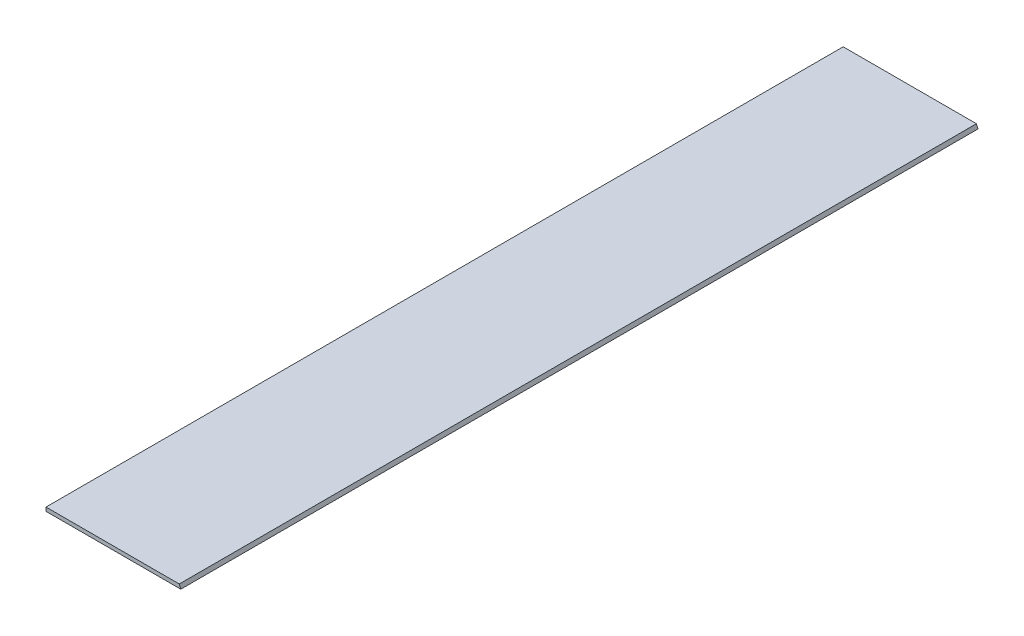
SolidWorks part; units mm, degrees
ref_plane "Front Plane" through (0, 0, 0) normal (0, 0, 1) x (1, 0, 0)
ref_plane "Top Plane" through (0, 0, 0) normal (0, 1, 0) x (1, 0, 0)
ref_plane "Right Plane" through (0, 0, 0) normal (1, 0, 0) x (0, 0, -1)
sketch "Sketch1" plane through (0, 0, 0) normal (0, 0, 1) x (1, 0, 0)
  line L0 (0, 0) -> (0, 2.3622)
  line L1 (0, 2.3622) -> (83.8575, 2.3622)
  line L2 (83.8575, 2.3622) -> (84.836, 0)
  line L3 (84.836, 0) -> (0, 0)
  dimension "D1" = 2.3622
  dimension "D2" = 67.5
  dimension "D3" = 84.836
extrude "Boss-Extrude1" add sketch "Sketch1" along normal blind 501.65
